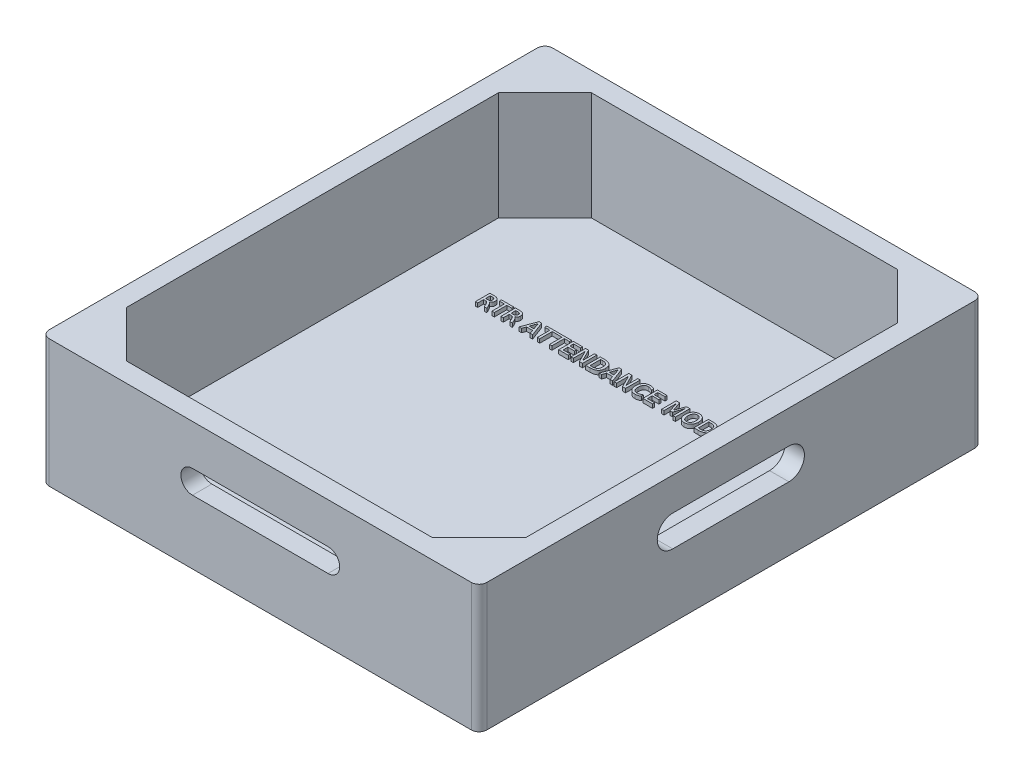
SolidWorks part; units mm, degrees
ref_plane "Front Plane" through (0, 0, 0) normal (0, 0, 1) x (1, 0, 0)
ref_plane "Top Plane" through (0, 0, 0) normal (0, 1, 0) x (1, 0, 0)
ref_plane "Right Plane" through (0, 0, 0) normal (1, 0, 0) x (0, 0, -1)
sketch "Sketch1" plane through (0, 0, 0) normal (0, 1, 0) x (1, 0, 0)
  line L1 (-56.5, 65) -> (56.5, 65)
  line L2 (-56.5, 65) -> (-56.5, -65)
  line L3 (-56.5, -65) -> (56.5, -65)
  line L4 (56.5, 65) -> (56.5, -65)
  line L5 (-56.5, 65) -> (56.5, -65) construction
  line L6 (-56.5, -65) -> (56.5, 65) construction
  point P0 (0, 0)
  dimension "D1" = 130
  dimension "D2" = 113
extrude "Boss-Extrude1" add sketch "Sketch1" along normal blind 33 contours L2 L3 L4 L1
sketch "Sketch3" plane through (0, 33, 0) normal (0, 1, 0) x (1, 0, 0)
  line L8 (51.5, 60) -> (-51.5, 60)
  line L9 (-51.5, 60) -> (-51.5, -60)
  line L10 (-51.5, -60) -> (51.5, -60)
  line L11 (51.5, -60) -> (51.5, 60)
  line L12 (51.5, 60) -> (-51.5, 60)
  line L13 (-51.5, 60) -> (-51.5, -60)
  line L14 (-51.5, -60) -> (51.5, -60)
  line L15 (51.5, -60) -> (51.5, 60)
  dimension "D1" = 5
extrude "Cut-Extrude1" cut sketch "Sketch3" against normal blind 28 contours L13 L14 L15 L12
fillet "Fillet1" radius 2 4 edges at (56.5, 16.5, -65) (56.5, 16.5, 65) (-56.5, 16.5, -65) (-56.5, 16.5, 65)
sketch "Sketch4" plane through (0, 5, 0) normal (0, 1, 0) x (1, 0, 0)
  text T0 "RTR ATTENDANCE MODULE" font "SolidWorks GDT" height in points 14
extrude "Boss-Extrude3" add sketch "Sketch4" along normal blind 1
sketch "Sketch5" plane through (0, 0, 65) normal (0, 0, 1) x (1, 0, 0)
  line L0 (-54.5, 16.5) -> (54.5, 16.5) construction
  line L1 (-54.5, 33) -> (-54.5, 0) construction
  line L2 (54.5, 0) -> (54.5, 33) construction
  line L3 (0, 0) -> (0, 33) construction
  line L4 (-54.5, 33) -> (54.5, 33) construction
  line L5 (-17.5, 19.5) -> (17.5, 19.5) construction
  line L6 (-17.5, 22.5) -> (17.5, 22.5)
  line L7 (-17.5, 16.5) -> (17.5, 16.5)
  arc A0 (-17.5, 22.5) -> (-17.5, 16.5) centre (-17.5, 19.5) ccw
  arc A1 (17.5, 16.5) -> (17.5, 22.5) centre (17.5, 19.5) ccw
  point P11 (0, 19.5)
  point P14 (0, 19.5)
extrude "Cut-Extrude2" cut sketch "Sketch5" against normal blind 5
sketch "Sketch6" plane through (56.5, 0, 0) normal (1, 0, 0) x (0, 0, -1)
  line L0 (-63, 16.5) -> (63, 16.5) construction
  line L1 (-63, 33) -> (-63, 0) construction
  line L2 (63, 0) -> (63, 33) construction
  line L3 (0, 0) -> (0, 33) construction
  line L4 (63, 0) -> (-63, 0) construction
  line L5 (63, 33) -> (-63, 33) construction
  line L6 (63, 16.5) -> (0, 16.5) construction
  line L7 (31.5, 16.5) -> (31.5, 0) construction
  line L8 (31.5, 16.5) -> (31.5, 33) construction
  line L9 (-15, 20.5) -> (15, 20.5) construction
  line L14 (-15, 24.5) -> (15, 24.5)
  line L15 (-15, 16.5) -> (15, 16.5)
  arc A0 (-15, 24.5) -> (-15, 16.5) centre (-15, 20.5) ccw
  arc A1 (15, 16.5) -> (15, 24.5) centre (15, 20.5) ccw
  point P15 (0, 20.5)
  point P19 (0, 20.5)
extrude "Cut-Extrude3" cut sketch "Sketch6" against normal blind 5
sketch "Sketch11" plane through (0, 5, 0) normal (0, 1, 0) x (1, 0, 0)
  line L0 (-51.5, 60) -> (-39.5, 60)
  line L1 (51.5, 60) -> (-51.5, 60) construction
  line L2 (-39.5, 60) -> (-51.5, 48)
  line L3 (-51.5, 60) -> (-51.5, -60) construction
  line L4 (-51.5, 48) -> (-51.5, 60)
  line L5 (0, 60) -> (0, -60) construction
  line L6 (-51.5, -60) -> (51.5, -60) construction
  line L7 (51.5, 0) -> (-51.5, 0) construction
  line L8 (51.5, -60) -> (51.5, 60) construction
  line L9 (51.5, 48) -> (51.5, 60)
  line L10 (51.5, 60) -> (39.5, 60)
  line L11 (39.5, 60) -> (51.5, 48)
  line L12 (39.5, -60) -> (51.5, -48)
  line L13 (51.5, -60) -> (39.5, -60)
  line L14 (51.5, -48) -> (51.5, -60)
  line L15 (-39.5, -60) -> (-51.5, -48)
  line L16 (-51.5, -60) -> (-39.5, -60)
  line L17 (-51.5, -48) -> (-51.5, -60)
  dimension "D1" = 12
  dimension "D2" = 12
extrude "Boss-Extrude4" add sketch "Sketch11" along normal blind 28 contours L2 L4 L0 | L15 L17 L16 | L12 L14 L13 | L11 L9 L10
sketch "Sketch15" plane through (0, 5, 0) normal (0, 1, 0) x (1, 0, 0)
  text T0 "SOHAM KARKHANIS" font "@Adobe Gothic Std B" height in points 10
extrude "Boss-Extrude5" add sketch "Sketch15" along normal blind 1
